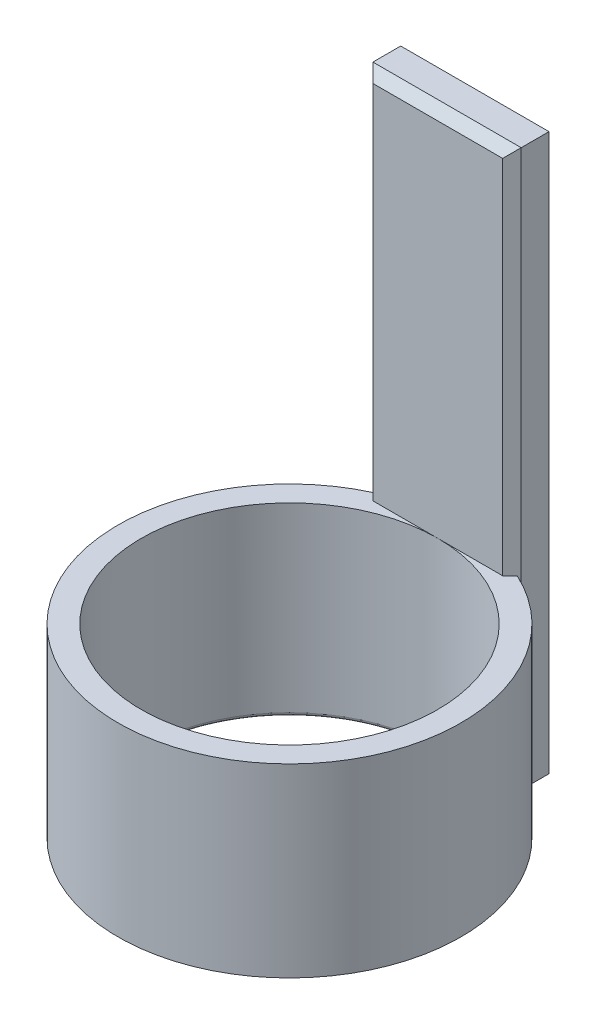
SolidWorks part; units mm, degrees
ref_plane "Front Plane" through (0, 0, 0) normal (0, 0, 1) x (1, 0, 0)
ref_plane "Top Plane" through (0, 0, 0) normal (0, 1, 0) x (1, 0, 0)
ref_plane "Right Plane" through (0, 0, 0) normal (1, 0, 0) x (0, 0, -1)
sketch "Sketch1" plane through (0, 0, 0) normal (0, 1, 0) x (1, 0, 0)
  circle A0 centre (0, 0) radius 8
  circle A1 centre (0, 0) radius 9.25
  dimension "D1" = 1.25
  dimension "D2" = 16
extrude "Boss-Extrude1" add sketch "Sketch1" along normal blind 10
ref_plane "Plane1" through (0, 0, -8) normal (0, 0, 1) x (1, 0, 0)
sketch "Sketch2" plane through (0, 0, -8) normal (0, 0, 1) x (1, 0, 0)
  line L0 (-9.25, 0) -> (9.25, 0) construction
  line L1 (4, 0) -> (-4, 0)
  line L2 (4, 0) -> (4, 30)
  line L3 (4, 30) -> (-4, 30)
  line L4 (-4, 0) -> (-4, 30)
  line L5 (4, 0) -> (-4, 30) construction
  line L6 (4, 30) -> (-4, 0) construction
  point P4 (0, 15)
  point P7 (-5.456, 0)
  point P8 (0, 0)
  dimension "D1" = 8
  dimension "D2" = 30
extrude "Boss-Extrude2" add sketch "Sketch2" against normal blind 2
fillet "Fillet1" radius 0.2 1 edges at (0, 0, 8)
chamfer "Chamfer1" distance 0.5 angle 45 3 edges at (-4, 20, -8) (0, 30, -8) (4, 20, -8)
